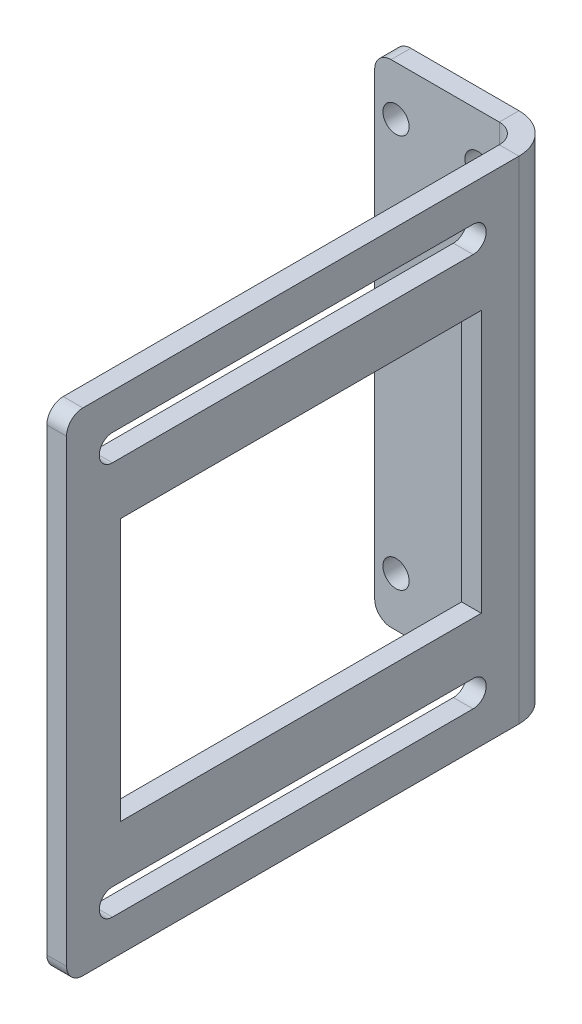
SolidWorks part; units mm, degrees
note: The reader was unsure of these and kept them because the rebuilt part matched: thickness of "Base-Flange1", "Edge-Flange1", "Sheet-Metal1", "Sheet-Metal2", "Sheet-Metal3", "Sheet-Metal4", "Sheet-Metal10"; flange length of "Edge-Flange1".
ref_plane "Front Plane" through (0, 0, 0) normal (0, 0, 1) x (1, 0, 0)
ref_plane "Top Plane" through (0, 0, 0) normal (0, 1, 0) x (1, 0, 0)
ref_plane "Right Plane" through (0, 0, 0) normal (1, 0, 0) x (0, 0, -1)
sketch "Sketch1" plane through (0, 0, 0) normal (0, 0, 1) x (1, 0, 0)
  line L0 (0, 0) -> (0, 150)
  line L1 (50, 150) -> (50, 0)
  line L2 (50, 0) -> (0, 0)
  line L3 (50, 150) -> (0, 150)
  line L4 (0, 75) -> (50, 75) construction
  line L5 (12.5, 0) -> (12.5, 150) construction
  line L6 (37.5, 150) -> (37.5, 0) construction
  dimension "D3" = 12.5
  dimension "D1" = 150
  dimension "D2" = 50
  dimension "D4" = 12.5
base flange "Base-Flange1" sketch "Sketch1" thickness 6 reverse thickness direction no parameters "D1"=4
edge flange "Edge-Flange1" sketch "Sketch8" flange angle 90 flange length 150 flange position material inside bend radius 6 thickness 6 relief rectangular parameters "D6"=10
sketch "Sketch8" plane through (50, 0, 0) normal (1, 0, 0) x (0, 1, 0)
  line L2 (0, 0) -> (0, 144)
  line L3 (0, 144) -> (150, 144)
  line L4 (150, 144) -> (150, 0)
  line L7 (0, 0) -> (150, 0) construction
  line L8 (0, 0) -> (150, 0)
bend "EdgeBend1" bend radius 6 bend angle 90 parameters "D5"=1
sketch "Sketch9" plane through (0, 0, 0) normal (0, 0, 1) x (1, 0, 0)
  line L0 (19, 150) -> (19, 0) construction
  line L1 (38, 150) -> (0, 150) construction
  line L2 (0, 0) -> (38, 0) construction
  line L3 (0, 75) -> (38, 75) construction
  line L4 (0, 150) -> (0, 0) construction
  line L5 (38, 150) -> (38, 0) construction
  line L6 (6.5, 150) -> (6.5, 0) construction
  line L7 (31.5, 150) -> (31.5, 0) construction
  circle A0 centre (6.5, 135) radius 4
  circle A1 centre (31.5, 135) radius 4
  circle A2 centre (6.5, 15) radius 4
  circle A3 centre (31.5, 15) radius 4
  dimension "D3" = 8
  dimension "D4" = 15
  dimension "D5" = 15
  dimension "D6" = 15
  dimension "D7" = 15
  dimension "D1" = 12.5
  dimension "D2" = 12.5
extrude "Cut-Extrude1" cut sketch "Sketch9" against normal up to surface (6 mm away) normal cut yes up to face at (19, 75, -6)
sketch "Sketch10" plane through (50, 0, 0) normal (1, 0, 0) x (0, 0, -1)
  line L0 (-75, 150) -> (-75, 0) construction
  line L1 (-6, 150) -> (-144, 150) construction
  line L2 (-144, 0) -> (-6, 0) construction
  line L3 (-144, 75) -> (-6, 75) construction
  line L4 (-144, 150) -> (-144, 0) construction
  line L5 (-6, 150) -> (-6, 0) construction
  line L6 (-130, 135) -> (-20, 135) construction
  line L7 (-130, 139) -> (-20, 139)
  line L8 (-6, 135) -> (-144, 135)
  line L9 (-6, 135) -> (-144, 135) construction
  line L10 (-130, 131) -> (-20, 131)
  line L11 (-144, 15) -> (-6, 15)
  line L12 (-144, 15) -> (-6, 15) construction
  line L13 (-130, 15) -> (-20, 15) construction
  line L14 (-130, 11) -> (-20, 11)
  line L15 (-130, 19) -> (-20, 19)
  arc A0 (-130, 139) -> (-130, 131) centre (-130, 135) ccw
  arc A1 (-20, 131) -> (-20, 139) centre (-20, 135) ccw
  arc A2 (-130, 11) -> (-130, 19) centre (-130, 15) cw
  arc A3 (-20, 19) -> (-20, 11) centre (-20, 15) cw
  point P14 (-75, 135)
  point P25 (-75, 15)
  dimension "D3" = 4
  dimension "D1" = 15
  dimension "90" = 110
  dimension "D2" = 15
extrude "Cut-Extrude2" cut sketch "Sketch10" against normal blind 10 normal cut yes
fillet "Fillet1" radius 5 4 edges at (47, 150, 144) (47, 0, 144) (0, 0, -3) (0, 150, -3)
sketch "Sketch11" plane through (50, 0, 0) normal (1, 0, 0) x (0, 0, -1)
  line L0 (-72.5, 150) -> (-72.5, 0) construction
  line L1 (-6, 150) -> (-139, 150) construction
  line L2 (-139, 0) -> (-6, 0) construction
  line L3 (-144, 75) -> (-6, 75) construction
  line L4 (-144, 145) -> (-144, 5) construction
  line L5 (-6, 150) -> (-6, 0) construction
  line L6 (-134, 135) -> (-16, 135) construction
  line L7 (-37.5, 0) -> (-107.5, 0)
  line L8 (-37.5, 0) -> (-37.5, 150)
  line L9 (-37.5, 150) -> (-107.5, 150)
  line L10 (-107.5, 0) -> (-107.5, 150)
  line L11 (-37.5, 0) -> (-107.5, 150) construction
  line L12 (-37.5, 150) -> (-107.5, 0) construction
  line L13 (-97.5, 50) -> (-47.5, 50) construction
  line L14 (-97.5, 50) -> (-97.5, 100) construction
  line L15 (-97.5, 100) -> (-47.5, 100) construction
  line L16 (-47.5, 50) -> (-47.5, 100) construction
  line L17 (-97.5, 50) -> (-47.5, 100) construction
  line L18 (-97.5, 100) -> (-47.5, 50) construction
  line L19 (-134, 15) -> (-16, 15) construction
  line L21 (-127.5, 35) -> (-17.5, 35)
  line L22 (-127.5, 35) -> (-127.5, 115)
  line L23 (-127.5, 115) -> (-17.5, 115)
  line L24 (-17.5, 35) -> (-17.5, 115)
  line L25 (-127.5, 35) -> (-17.5, 115) construction
  line L26 (-127.5, 115) -> (-17.5, 35) construction
  circle A0 centre (-72.5, 75) radius 20
  circle A1 centre (-97.5, 100) radius 4
  circle A2 centre (-47.5, 100) radius 4
  circle A3 centre (-47.5, 50) radius 4
  circle A4 centre (-97.5, 50) radius 4
  arc A5 (-130, 139) -> (-130, 131) centre (-130, 135) ccw construction
  arc A6 (-20, 131) -> (-20, 139) centre (-20, 135) ccw construction
  arc A7 (-130, 19) -> (-130, 11) centre (-130, 15) ccw construction
  arc A8 (-20, 11) -> (-20, 19) centre (-20, 15) ccw construction
  circle A9 centre (-47.5, 135) radius 4
  circle A10 centre (-97.5, 135) radius 4
  circle A11 centre (-47.5, 15) radius 4
  circle A12 centre (-97.5, 15) radius 4
  point P12 (-72.5, 75)
  dimension "D2" = 50
  dimension "D3" = 8
  dimension "D4" = 8
  dimension "D5" = 10
  dimension "D6" = 10
  dimension "D7" = 10
  dimension "D8" = 10
  dimension "D1" = 70
  dimension "D9" = 80
  dimension "D10" = 110
extrude "Cut-Extrude5" cut sketch "Sketch11" against normal blind 10 contours L23 L22 L21 L10 | L21 L24 L23 L8 | A2 | A3 | A0 | L23 L10 L21 L8 A4 A3 A2 A1 A0
sketch "Bend-Lines1" [suppressed] plane through (0, 0, 0) normal (0, 1, 0) x (1, 0, 0)
sketch "Bounding-Box1" [suppressed] plane through (0, 0, 0) normal (0, 1, 0) x (1, 0, 0)
sheet metal parameters "Sheet-Metal1" thickness 6 parameters "D1"=4
flat pattern "Flat-Pattern1" [suppressed]
sketch "Bend-Lines2" plane through (0, 0, 0) normal (0, 1, 0) x (1, 0, 0)
sketch3d "Bounding-Box2" [suppressed]
  line L0 (50, 150, 0) -> (50, 0, 0) construction
  line L1 (0, 150, 0) -> (0, 0, 0) construction
  line L2 (50, 150, 0) -> (0, 150, 0) construction
  line L3 (50, 0, 0) -> (0, 0, 0) construction
sheet metal parameters "Sheet-Metal2" thickness 6 parameters "D1"=4, "D7"=4
flat pattern "Flat-Pattern1" [suppressed]
sketch "Bend-Lines2" plane through (0, 0, 0) normal (0, 0, 1) x (1, 0, 0)
  line L0 (47.4504, 0) -> (47.4504, 150) construction
  line L1 (47.4504, 0) -> (47.4504, 150) construction
sketch3d "Bounding-Box2" [suppressed]
  line L0 (0, 0, 0) -> (164.9008, 0, 0) construction
  line L1 (0, 150, 0) -> (164.9008, 150, 0) construction
  line L2 (0, 0, 0) -> (0, 150, 0) construction
  line L3 (164.9008, 0, 0) -> (164.9008, 150, 0) construction
bend of the flat pattern "Flatten-<EdgeBend1>1"
sheet metal parameters "Sheet-Metal3" thickness 6 parameters "D1"=4, "D7"=4
flat pattern "Flat-Pattern1" [suppressed]
sketch "Bend-Lines2" plane through (0, 0, 0) normal (0, 0, 1) x (1, 0, 0)
  line L0 (47.4504, 0) -> (47.4504, 150) construction
  line L1 (47.4504, 0) -> (47.4504, 150) construction
sketch3d "Bounding-Box2" [suppressed]
  line L0 (0, 0, 0) -> (164.9008, 0, 0) construction
  line L1 (0, 150, 0) -> (164.9008, 150, 0) construction
  line L2 (0, 0, 0) -> (0, 150, 0) construction
  line L3 (164.9008, 0, 0) -> (164.9008, 150, 0) construction
bend of the flat pattern "Flatten-<EdgeBend1>1"
sheet metal parameters "Sheet-Metal4" thickness 6 parameters "D1"=4, "D7"=4
flat pattern "Flat-Pattern1" [suppressed]
sketch "Bend-Lines2" plane through (0, 0, 0) normal (0, 0, 1) x (1, 0, 0)
  line L0 (47.4504, 0) -> (47.4504, 150) construction
  line L1 (47.4504, 0) -> (47.4504, 150) construction
sketch3d "Bounding-Box2" [suppressed]
  line L0 (0, 150, 0) -> (164.9008, 150, 0) construction
  line L1 (0, 0, 0) -> (164.9008, 0, 0) construction
  line L2 (0, 150, 0) -> (0, 0, 0) construction
  line L3 (164.9008, 150, 0) -> (164.9008, 0, 0) construction
sketch "Sketch11-1" [suppressed] plane through (48.9008, 0, -4) normal (0, 0, -1) x (-1, 0, 0)
  line L0 (-55.8683, 150) -> (-55.8683, 0) construction
  line L3 (-116, 75) -> (-0.7366, 75) construction
  line L6 (-107.3683, 135) -> (-9.3683, 135) construction
  line L7 (-20.8683, 0) -> (-90.8683, 0)
  line L8 (-20.8683, 0) -> (-20.8683, 150)
  line L9 (-20.8683, 150) -> (-90.8683, 150)
  line L10 (-90.8683, 0) -> (-90.8683, 150)
  line L11 (-20.8683, 0) -> (-90.8683, 150) construction
  line L12 (-20.8683, 150) -> (-90.8683, 0) construction
  line L13 (-80.8683, 50) -> (-30.8683, 50) construction
  line L14 (-80.8683, 50) -> (-80.8683, 100) construction
  line L15 (-80.8683, 100) -> (-30.8683, 100) construction
  line L16 (-30.8683, 50) -> (-30.8683, 100) construction
  line L17 (-80.8683, 50) -> (-30.8683, 100) construction
  line L18 (-80.8683, 100) -> (-30.8683, 50) construction
  line L19 (-107.3683, 15) -> (-9.3683, 15) construction
  line L21 (-100.8683, 35) -> (-10.8683, 35)
  line L22 (-100.8683, 35) -> (-100.8683, 115)
  line L23 (-100.8683, 115) -> (-10.8683, 115)
  line L24 (-10.8683, 35) -> (-10.8683, 115)
  line L25 (-100.8683, 35) -> (-10.8683, 115) construction
  line L26 (-100.8683, 115) -> (-10.8683, 35) construction
  circle A0 centre (-55.8683, 75) radius 20
  circle A1 centre (-80.8683, 100) radius 4
  circle A2 centre (-30.8683, 100) radius 4
  circle A3 centre (-30.8683, 50) radius 4
  circle A4 centre (-80.8683, 50) radius 4
  circle A9 centre (-30.8683, 135) radius 4
  circle A10 centre (-80.8683, 135) radius 4
  circle A11 centre (-30.8683, 15) radius 4
  circle A12 centre (-80.8683, 15) radius 4
  point P12 (-55.8683, 75)
  dimension "D2" = 50
  dimension "D3" = 8
  dimension "D4" = 8
  dimension "D5" = 10
  dimension "D6" = 10
  dimension "D7" = 10
  dimension "D8" = 10
  dimension "D1" = 70
  dimension "D9" = 80
  dimension "D10" = 90
bend of the flat pattern "Flatten-<EdgeBend1>1"
sheet metal parameters "Sheet-Metal10" thickness 6 parameters "D1"=4, "D7"=4
flat pattern "Flat-Pattern1" [suppressed]
sketch "Bend-Lines2" plane through (0, 0, 0) normal (0, 0, 1) x (1, 0, 0)
  line L0 (45.0012, 0) -> (45.0012, 150) construction
  line L1 (45.0012, 0) -> (45.0012, 150) construction
sketch3d "Bounding-Box2" [suppressed]
  line L0 (0, 150, 0) -> (190.0024, 150, 0) construction
  line L1 (0, 0, 0) -> (190.0024, 0, 0) construction
  line L2 (0, 150, 0) -> (0, 0, 0) construction
  line L3 (190.0024, 150, 0) -> (190.0024, 0, 0) construction
bend of the flat pattern "Flatten-<EdgeBend1>1"
sketch "Sketch11-1" plane through (46.0024, 0, -6) normal (0, 0, -1) x (-1, 0, 0)
  line L0 (-72.5, 150) -> (-72.5, 0) construction
  line L3 (-144, 75) -> (-6, 75) construction
  line L6 (-134, 135) -> (-16, 135) construction
  line L7 (-37.5, 0) -> (-107.5, 0)
  line L8 (-37.5, 0) -> (-37.5, 150)
  line L9 (-37.5, 150) -> (-107.5, 150)
  line L10 (-107.5, 0) -> (-107.5, 150)
  line L11 (-37.5, 0) -> (-107.5, 150) construction
  line L12 (-37.5, 150) -> (-107.5, 0) construction
  line L13 (-97.5, 50) -> (-47.5, 50) construction
  line L14 (-97.5, 50) -> (-97.5, 100) construction
  line L15 (-97.5, 100) -> (-47.5, 100) construction
  line L16 (-47.5, 50) -> (-47.5, 100) construction
  line L17 (-97.5, 50) -> (-47.5, 100) construction
  line L18 (-97.5, 100) -> (-47.5, 50) construction
  line L19 (-134, 15) -> (-16, 15) construction
  line L21 (-127.5, 35) -> (-17.5, 35)
  line L22 (-127.5, 35) -> (-127.5, 115)
  line L23 (-127.5, 115) -> (-17.5, 115)
  line L24 (-17.5, 35) -> (-17.5, 115)
  line L25 (-127.5, 35) -> (-17.5, 115) construction
  line L26 (-127.5, 115) -> (-17.5, 35) construction
  circle A0 centre (-72.5, 75) radius 20
  circle A1 centre (-97.5, 100) radius 4
  circle A2 centre (-47.5, 100) radius 4
  circle A3 centre (-47.5, 50) radius 4
  circle A4 centre (-97.5, 50) radius 4
  circle A9 centre (-47.5, 135) radius 4
  circle A10 centre (-97.5, 135) radius 4
  circle A11 centre (-47.5, 15) radius 4
  circle A12 centre (-97.5, 15) radius 4
  point P12 (-72.5, 75)
  dimension "D2" = 50
  dimension "D3" = 8
  dimension "D4" = 8
  dimension "D5" = 10
  dimension "D6" = 10
  dimension "D7" = 10
  dimension "D8" = 10
  dimension "D1" = 70
  dimension "D9" = 80
  dimension "D10" = 110
